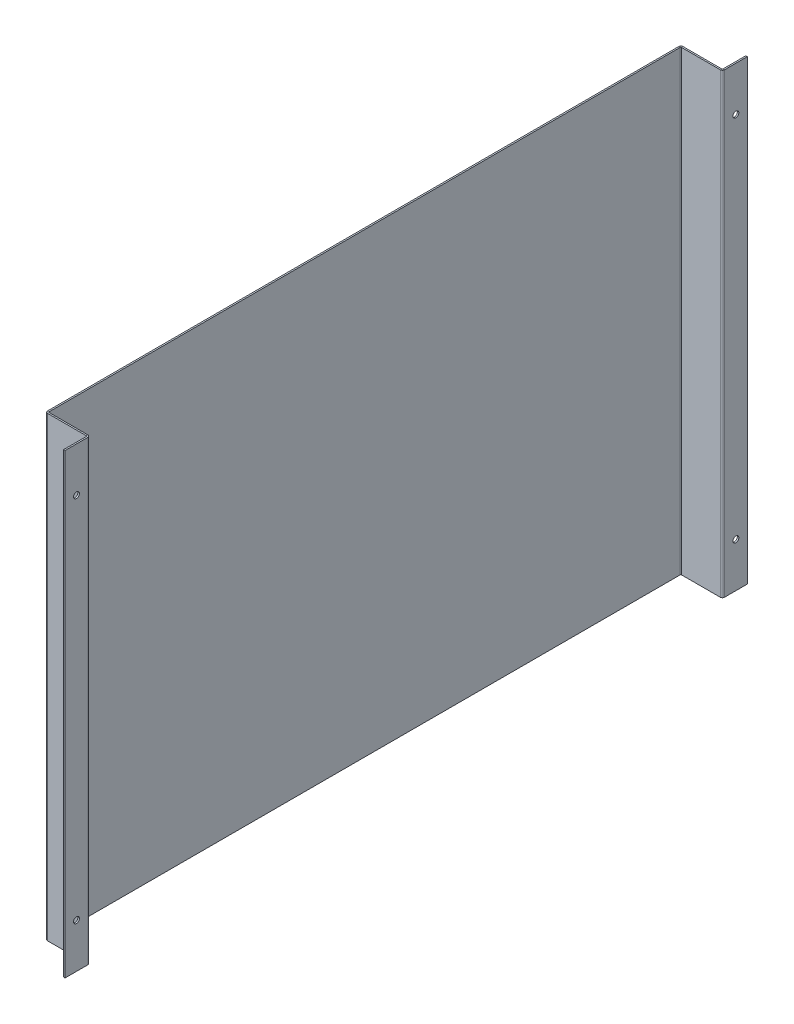
SolidWorks part; units mm, degrees
note: The reader was unsure of these and kept them because the rebuilt part matched: flange length of "Edge-Flange1", "Edge-Flange2".
ref_plane "Front Plane" through (0, 0, 0) normal (0, 0, 1) x (1, 0, 0)
ref_plane "Top Plane" through (0, 0, 0) normal (0, 1, 0) x (1, 0, 0)
ref_plane "Right Plane" through (0, 0, 0) normal (1, 0, 0) x (0, 0, -1)
sketch "Sketch1" plane through (0, 0, 0) normal (1, 0, 0) x (0, 0, -1)
  line L1 (-382.5, -275) -> (382.5, -275)
  line L2 (-382.5, -275) -> (-382.5, 275)
  line L3 (-382.5, 275) -> (382.5, 275)
  line L4 (382.5, -275) -> (382.5, 275)
  line L5 (-382.5, -275) -> (382.5, 275) construction
  line L6 (-382.5, 275) -> (382.5, -275) construction
  point P0 (0, 0)
  dimension "D1" = 765
  dimension "D2" = 550
base flange "Base-Flange1" sketch "Sketch1" thickness 1.8 reverse thickness direction no parameters "D1"=0.7366
edge flange "Edge-Flange1" sketch "Sketch10" flange profiles "Sketch10", "Sketch11" flange angle 90 flange length 50 flange position material inside bend radius 0.7366 thickness 1.8 relief rectangular parameters "D6"=10, "D8"=1
sketch "Sketch10" plane through (0, 0, 382.5) normal (0, 0, -1) x (0, 1, 0)
  line L1 (275, 0) -> (-275, 0) construction
  line L2 (-275, 0) -> (-275, 48.2)
  line L3 (-275, 48.2) -> (275, 48.2)
  line L4 (275, 48.2) -> (275, 0)
  line L5 (275, 0) -> (-275, 0)
sketch "Sketch11" plane through (0, 0, -382.5) normal (0, 0, 1) x (0, -1, 0)
  line L1 (275, 0) -> (-275, 0) construction
  line L2 (-275, 0) -> (-275, 48.2)
  line L3 (-275, 48.2) -> (275, 48.2)
  line L4 (275, 48.2) -> (275, 0)
  line L5 (275, 0) -> (-275, 0)
bend "EdgeBend1" bend radius 0.7366 bend angle 90 parameters "D5"=1
bend "EdgeBend2" bend radius 0.7366 bend angle 90 parameters "D5"=2
edge flange "Edge-Flange2" sketch "Sketch16" flange profiles "Sketch16", "Sketch17" flange angle 90 flange length 30 flange position material outside bend radius 0.7366 thickness 1.8 relief rectangular parameters "D6"=10, "D8"=1
sketch "Sketch16" plane through (48.2, 0, -382.5) normal (1, 0, 0) x (0, -1, 0)
  line L2 (-275, 0) -> (-275, 28.2)
  line L3 (-275, 28.2) -> (275, 28.2)
  line L4 (275, 28.2) -> (275, 0)
  line L7 (275, 0) -> (-275, 0) construction
  line L8 (275, 0) -> (-275, 0)
sketch "Sketch17" plane through (48.2, 0, 382.5) normal (1, 0, 0) x (0, 1, 0)
  line L1 (275, 0) -> (-275, 0) construction
  line L2 (275, 0) -> (275, 28.2)
  line L3 (275, 28.2) -> (-275, 28.2)
  line L4 (-275, 28.2) -> (-275, 0)
  line L5 (275, 0) -> (-275, 0)
bend "EdgeBend3" bend radius 0.7366 bend angle 90 parameters "D5"=3
bend "EdgeBend4" bend radius 0.7366 bend angle 90 parameters "D5"=4
sketch "Sketch18" plane through (48.2, 0, 0) normal (-1, 0, 0) x (0, 0, 1)
  line L1 (-410.7, 275) -> (-383.2366, 275) construction
  line L3 (-383.2366, -275) -> (-410.7, -275) construction
  circle A0 centre (-396.9683, 221.5) radius 6.5 construction
  circle A1 centre (-396.9683, -221.5) radius 6.5 construction
  circle A2 centre (-396.9683, 221.5) radius 3.5
  circle A3 centre (-396.9683, -221.5) radius 3.5
  point P8 (-396.9683, -275)
  dimension "D1" = 13
  dimension "D2" = 13
  dimension "D3" = 60
  dimension "D4" = 60
  dimension "D5" = 7
extrude "Cut-Extrude1" cut sketch "Sketch18" against normal blind 10
mirror "Mirror1" about plane through (0, 0, 0) normal (0, 0, 1) of "Cut-Extrude1"
sketch "Bend-Lines1" [suppressed] plane through (0, 0, 0) normal (0, 1, 0) x (1, 0, 0)
sketch "Bounding-Box1" [suppressed] plane through (0, 0, 0) normal (0, 1, 0) x (1, 0, 0)
sheet metal parameters "Sheet-Metal1" thickness 1.8 parameters "D1"=0.7366
flat pattern "Flat-Pattern1" [suppressed]
sketch "Bend-Lines2" plane through (0, 0, 0) normal (0, 1, 0) x (1, 0, 0)
sketch3d "Bounding-Box2" [suppressed]
  line L0 (-382.5, -275, 0) -> (382.5, -275, 0) construction
  line L1 (-382.5, 275, 0) -> (382.5, 275, 0) construction
  line L2 (-382.5, -275, 0) -> (-382.5, 275, 0) construction
  line L3 (382.5, -275, 0) -> (382.5, 275, 0) construction
sheet metal parameters "Sheet-Metal2" thickness 1.8 parameters "D1"=0.7366
flat pattern "Flat-Pattern1"
sketch "Bend-Lines2" plane through (0, 0, 0) normal (1, 0, 0) x (0, 0, -1)
  line L0 (381.2488, -275) -> (381.2488, 275) construction
  line L1 (-381.2488, 275) -> (-381.2488, -275) construction
  line L2 (381.2488, -275) -> (381.2488, 275) construction
  line L3 (-381.2488, 275) -> (-381.2488, -275) construction
sketch3d "Bounding-Box2" [suppressed]
  line L0 (429.9976, -275, 0) -> (-429.9976, -275, 0) construction
  line L1 (429.9976, 275, 0) -> (-429.9976, 275, 0) construction
  line L2 (429.9976, -275, 0) -> (429.9976, 275, 0) construction
  line L3 (-429.9976, -275, 0) -> (-429.9976, 275, 0) construction
bend of the flat pattern "Flatten-<EdgeBend1>1"
bend of the flat pattern "Flatten-<EdgeBend2>1"
sheet metal parameters "Sheet-Metal3" thickness 1.8 parameters "D1"=0.7366
flat pattern "Flat-Pattern1"
sketch "Bend-Lines2" plane through (0, 0, 0) normal (1, 0, 0) x (0, 0, -1)
  line L0 (381.2488, -275) -> (381.2488, 275) construction
  line L1 (-381.2488, 275) -> (-381.2488, -275) construction
  line L2 (381.2488, -275) -> (381.2488, 275) construction
  line L3 (-381.2488, 275) -> (-381.2488, -275) construction
  line L4 (-428.7463, 275) -> (-428.7463, -275) construction
  line L5 (428.7463, -275) -> (428.7463, 275) construction
  line L6 (-428.7463, 275) -> (-428.7463, -275) construction
  line L7 (428.7463, -275) -> (428.7463, 275) construction
sketch3d "Bounding-Box2" [suppressed]
  line L0 (457.4951, -275, 0) -> (-457.4951, -275, 0) construction
  line L1 (457.4951, 275, 0) -> (-457.4951, 275, 0) construction
  line L2 (457.4951, -275, 0) -> (457.4951, 275, 0) construction
  line L3 (-457.4951, -275, 0) -> (-457.4951, 275, 0) construction
bend of the flat pattern "Flatten-<EdgeBend1>1"
bend of the flat pattern "Flatten-<EdgeBend2>1"
bend of the flat pattern "Flatten-<EdgeBend3>1"
bend of the flat pattern "Flatten-<EdgeBend4>1"
sheet metal parameters "Sheet-Metal4" thickness 1.8 parameters "D1"=0.7366
flat pattern "Flat-Pattern1"
sketch "Bend-Lines2" plane through (0, 0, 0) normal (1, 0, 0) x (0, 0, -1)
  line L0 (381.2488, -275) -> (381.2488, 275) construction
  line L1 (-381.2488, 275) -> (-381.2488, -275) construction
  line L2 (381.2488, -275) -> (381.2488, 275) construction
  line L3 (-381.2488, 275) -> (-381.2488, -275) construction
  line L4 (-428.7463, 275) -> (-428.7463, -275) construction
  line L5 (428.7463, -275) -> (428.7463, 275) construction
  line L6 (-428.7463, 275) -> (-428.7463, -275) construction
  line L7 (428.7463, -275) -> (428.7463, 275) construction
sketch3d "Bounding-Box2" [suppressed]
  line L0 (457.4951, -275, 0) -> (-457.4951, -275, 0) construction
  line L1 (457.4951, 275, 0) -> (-457.4951, 275, 0) construction
  line L2 (457.4951, -275, 0) -> (457.4951, 275, 0) construction
  line L3 (-457.4951, -275, 0) -> (-457.4951, 275, 0) construction
bend of the flat pattern "Flatten-<EdgeBend1>1"
bend of the flat pattern "Flatten-<EdgeBend2>1"
bend of the flat pattern "Flatten-<EdgeBend3>1"
bend of the flat pattern "Flatten-<EdgeBend4>1"
sheet metal parameters "Sheet-Metal5" thickness 1.8 parameters "D1"=0.7366
flat pattern "Flat-Pattern1"
sketch "Bend-Lines2" plane through (0, 0, 0) normal (1, 0, 0) x (0, 0, -1)
  line L0 (381.2488, -275) -> (381.2488, 275) construction
  line L1 (-381.2488, 275) -> (-381.2488, -275) construction
  line L2 (381.2488, -275) -> (381.2488, 275) construction
  line L3 (-381.2488, 275) -> (-381.2488, -275) construction
  line L4 (-430.5463, 275) -> (-430.5463, -275) construction
  line L5 (430.5463, -275) -> (430.5463, 275) construction
  line L6 (-430.5463, 275) -> (-430.5463, -275) construction
  line L7 (430.5463, -275) -> (430.5463, 275) construction
sketch3d "Bounding-Box2" [suppressed]
  line L0 (459.2951, -275, 0) -> (-459.2951, -275, 0) construction
  line L1 (459.2951, 275, 0) -> (-459.2951, 275, 0) construction
  line L2 (459.2951, -275, 0) -> (459.2951, 275, 0) construction
  line L3 (-459.2951, -275, 0) -> (-459.2951, 275, 0) construction
bend of the flat pattern "Flatten-<EdgeBend1>1"
bend of the flat pattern "Flatten-<EdgeBend2>1"
bend of the flat pattern "Flatten-<EdgeBend3>1"
bend of the flat pattern "Flatten-<EdgeBend4>1"
